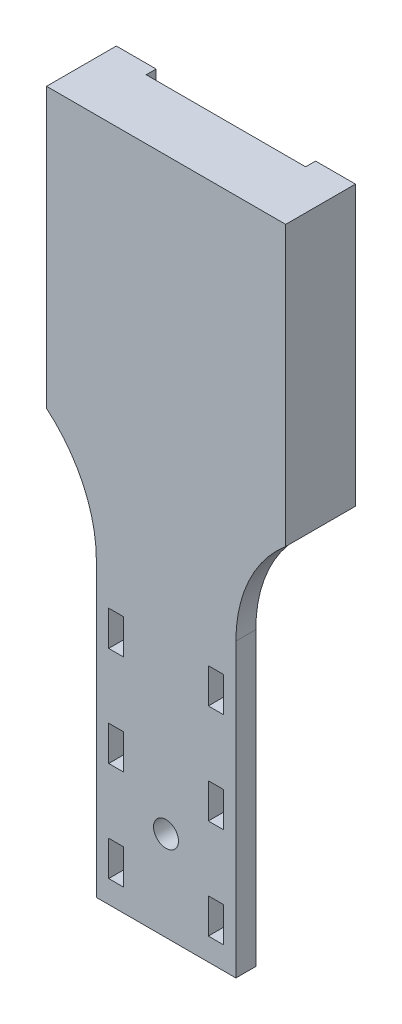
SolidWorks part; units mm, degrees
ref_plane "Front Plane" through (0, 0, 0) normal (0, 0, 1) x (1, 0, 0)
ref_plane "Top Plane" through (0, 0, 0) normal (0, 1, 0) x (1, 0, 0)
ref_plane "Right Plane" through (0, 0, 0) normal (1, 0, 0) x (0, 0, -1)
sketch "Sketch1" plane through (0, 0, 0) normal (0, 1, 0) x (1, 0, 0)
  line L9 (0, 0) -> (24, 0)
  line L10 (0, 0) -> (0, 6)
  line L11 (0, 6) -> (24, 6)
  line L12 (24, 0) -> (24, 6)
  dimension "D1" = 24
  dimension "D2" = 6
extrude "Boss-Extrude1" add sketch "Sketch1" along normal blind 27
sketch "Sketch2" plane through (0, 27, 0) normal (0, 1, 0) x (1, 0, 0)
  line L0 (0, 6) -> (0, 0) construction
  line L1 (1, 1) -> (23, 1)
  line L2 (1, 1) -> (1, 5)
  line L3 (1, 5) -> (4, 5)
  line L4 (23, 1) -> (23, 5)
  line L5 (0, 0) -> (24, 0) construction
  line L6 (20, 5) -> (23, 5)
  line L7 (4, 7.6227) -> (20, 7.6227)
  line L8 (4, 7.6227) -> (4, 5)
  line L10 (20, 7.6227) -> (20, 5)
  dimension "D1" = 22
  dimension "D2" = 1
  dimension "D3" = 1
  dimension "D4" = 16
  dimension "D5" = 4
  dimension "D6" = 4
extrude "Cut-Extrude1" cut sketch "Sketch2" against normal blind 27
sketch "Sketch3" plane through (0, 27, 0) normal (0, 1, 0) x (1, 0, 0)
  line L4 (24, 0) -> (24, 5)
  line L5 (24, 0) -> (24, 6) construction
  line L6 (24, 0) -> (0, 0)
  line L7 (0, 6) -> (4, 6)
  line L8 (0, 6) -> (0, 5)
  line L10 (4, 6) -> (4, 5)
  line L11 (20, 6) -> (24, 6)
  line L12 (20, 6) -> (20, 5)
  line L14 (24, 6) -> (24, 5)
  line L15 (0, 0) -> (0, 5)
  line L16 (4, 5) -> (20, 5)
extrude "Boss-Extrude2" add sketch "Sketch3" along normal blind 1
sketch "Sketch4" plane through (0, 0, 0) normal (0, -1, 0) x (1, 0, 0)
  line L1 (1, -5) -> (4, -5)
  line L2 (1, -5) -> (1, -6)
  line L3 (1, -6) -> (4, -6)
  line L4 (4, -5) -> (4, -6)
  line L5 (23, -5) -> (20, -5)
  line L6 (23, -5) -> (23, -6)
  line L7 (23, -6) -> (20, -6)
  line L8 (20, -5) -> (20, -6)
extrude "Cut-Extrude2" cut sketch "Sketch4" against normal blind 8
fillet "Fillet1" radius 1 2 edges at (23, 8, -5.5) (1, 8, -5.5)
sketch "Sketch5" plane through (0, 0, 0) normal (0, 0, 1) x (1, 0, 0)
  line L0 (0, 0) -> (24, 0) construction
  line L1 (5, 0) -> (19, 0)
  line L2 (5, 0) -> (5, -40)
  line L3 (5, -40) -> (19, -40)
  line L4 (19, 0) -> (19, -40)
  line L5 (0, 28) -> (0, 0) construction
  point P8 (5, -20)
  dimension "D1" = 14
  dimension "D2" = 5
  dimension "D3" = 40
extrude "Boss-Extrude3" add sketch "Sketch5" against normal up to surface (1 mm away) up to face at (12, 13.5, -1)
sketch "Sketch7" plane through (0, 0, 0) normal (0, 0, 1) x (1, 0, 0)
  line L6 (0, 28) -> (0, 0)
  line L7 (5, 0) -> (5, -40)
  line L8 (5, -40) -> (19, -40)
  line L9 (19, -40) -> (19, 0)
  line L10 (24, 0) -> (24, 28)
  line L11 (24, 28) -> (0, 28)
  line L12 (0, 28) -> (0, 0)
  line L13 (5, 0) -> (5, -40)
  line L14 (5, -40) -> (19, -40)
  line L15 (19, -40) -> (19, 0)
  line L16 (24, 0) -> (24, 28)
  line L17 (24, 28) -> (0, 28)
  line L20 (0, 0) -> (5, 0)
  line L21 (0, 0) -> (5, 0)
  line L22 (19, 0) -> (24, 0)
  line L23 (19, 0) -> (24, 0)
  dimension "D1" = 0
extrude "Boss-Extrude4" add sketch "Sketch7" along normal blind 1
fillet "Fillet2" radius 14 2 edges at (19, 0, 0) (5, 0, 0)
sketch "Sketch6" plane through (0, 0, -1) normal (0, 0, -1) x (-1, 0, 0)
  line L0 (-7.7364, -34.2375) -> (-6.2364, -34.2375)
  line L1 (-17.7364, -34.2375) -> (-16.2364, -34.2375)
  line L2 (-17.7364, -34.2375) -> (-17.7364, -37.7375)
  line L3 (-17.7364, -37.7375) -> (-16.2364, -37.7375)
  line L4 (-16.2364, -34.2375) -> (-16.2364, -37.7375)
  line L5 (-6.2364, -34.2375) -> (-6.2364, -37.7375)
  line L6 (-7.7364, -34.2375) -> (-7.7364, -37.7375)
  line L7 (-7.7364, -37.7375) -> (-6.2364, -37.7375)
  line L8 (-7.7364, -24.2375) -> (-6.2364, -24.2375)
  line L9 (-6.2364, -24.2375) -> (-6.2364, -27.7375)
  line L10 (-7.7364, -24.2375) -> (-7.7364, -27.7375)
  line L11 (-7.7364, -27.7375) -> (-6.2364, -27.7375)
  line L12 (-17.7364, -24.2375) -> (-16.2364, -24.2375)
  line L13 (-16.2364, -24.2375) -> (-16.2364, -27.7375)
  line L14 (-17.7364, -24.2375) -> (-17.7364, -27.7375)
  line L15 (-17.7364, -27.7375) -> (-16.2364, -27.7375)
  line L16 (-17.7364, -14.2375) -> (-16.2364, -14.2375)
  line L17 (-16.2364, -14.2375) -> (-16.2364, -17.7375)
  line L18 (-17.7364, -14.2375) -> (-17.7364, -17.7375)
  line L19 (-17.7364, -17.7375) -> (-16.2364, -17.7375)
  line L20 (-7.7364, -14.2375) -> (-6.2364, -14.2375)
  line L21 (-6.2364, -14.2375) -> (-6.2364, -17.7375)
  line L22 (-7.7364, -14.2375) -> (-7.7364, -17.7375)
  line L23 (-7.7364, -17.7375) -> (-6.2364, -17.7375)
  dimension "D1" = 1.5
  dimension "D2" = 3.5
extrude "Cut-Extrude3" cut sketch "Sketch6" against normal blind 3
hole_wizard "Tap Drill for M3x0.5 Tap1" positions "Sketch8" profile "Sketch9" hole size "M3x0.5" standard "ANSI Metric" end condition through all
sketch "Sketch8" plane through (0, 0, 1) normal (0, 0, 1) x (1, 0, 0)
  point P0 (11.9864, -30.9875)
sketch "Sketch9" plane through (11.9864, -30.9875, 1) normal (1, 0, 0) x (0, -1, 0)
  line L0 (0, 0) -> (0, 7)
  line L1 (0, 7) -> (1.25, 7)
  line L2 (1.25, 7) -> (1.25, 0)
  line L5 (1.25, 0) -> (0, 0)
  line L11 (0, -6.35) -> (0, 107.95) construction
  dimension "Thru Hole Dia." = 2.5
  dimension "Thru Hole Depth" = 7
fillet "Fillet3" radius 0.5 4 edges at (23, -0.9258, -3.5) (1, -0.9258, -3.5) (20, 8, -5.5) (4, 8, -5.5)
